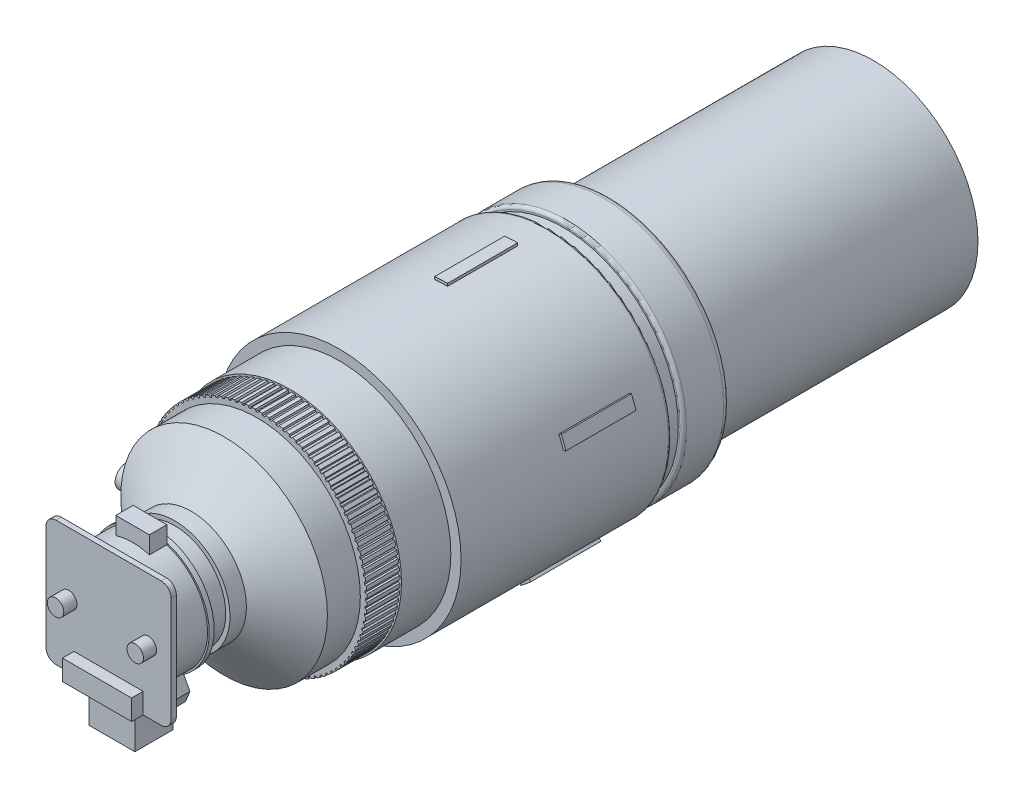
SolidWorks part; units mm, degrees
ref_plane "Front Plane" through (0, 0, 0) normal (0, 0, 1) x (1, 0, 0)
ref_plane "Top Plane" through (0, 0, 0) normal (0, 1, 0) x (1, 0, 0)
ref_plane "Right Plane" through (0, 0, 0) normal (1, 0, 0) x (0, 0, -1)
sketch "Sketch1" plane through (0, 0, 0) normal (0, 0, 1) x (1, 0, 0)
  circle A0 centre (0, 0) radius 31.75
  dimension "D1" = 63.5
extrude "Boss-Extrude1" add sketch "Sketch1" along normal blind 80
sketch "Sketch2" plane through (0, 0, 80) normal (0, 0, 1) x (1, 0, 0)
  circle A0 centre (0, 0) radius 36.5
  dimension "D1" = 73
extrude "Boss-Extrude2" add sketch "Sketch2" along normal blind 14.3
fillet "Fillet1" radius 2 1 edges at (36.5, 0, 80)
sketch "Sketch3" plane through (0, 0, 94.3) normal (0, 0, 1) x (1, 0, 0)
  circle A0 centre (0, 0) radius 35
  dimension "D1" = 70
extrude "Boss-Extrude3" add sketch "Sketch3" along normal blind 4
sketch "Sketch4" plane through (0, 0, 98.3) normal (0, 0, 1) x (1, 0, 0)
  circle A0 centre (0, 0) radius 37
  dimension "D1" = 74
extrude "Boss-Extrude4" add sketch "Sketch4" along normal blind 64
fillet "Fillet2" radius 1 2 edges at (37, 0, 98.3) (36.5, 0, 94.3)
sketch "Sketch5" plane through (0, 0, 162.3) normal (0, 0, 1) x (1, 0, 0)
  circle A0 centre (0, 0) radius 33.9
  dimension "D1" = 67.8
extrude "Boss-Extrude5" add sketch "Sketch5" along normal blind 15
sketch "Sketch6" plane through (0, 0, 177.3) normal (0, 0, 1) x (1, 0, 0)
  circle A0 centre (0, 0) radius 33.4
  dimension "D1" = 66.8
extrude "Boss-Extrude6" add sketch "Sketch6" along normal blind 10
sketch "Sketch7" plane through (0, 0, 187.3) normal (0, 0, 1) x (1, 0, 0)
  line L0 (0, 0) -> (0, 33.4) construction
  line L1 (-0.5, 33.3963) -> (-0.3, 32.9)
  line L2 (-0.3, 32.9) -> (0, 32.9)
  line L3 (0, 32.9) -> (0.3, 32.9)
  line L4 (0.3, 32.9) -> (0.5, 33.3963)
  circle A0 centre (0, 0) radius 33.4 construction
  circle A1 centre (0, 0) radius 33.4
  circle M6 centre (0, 0) radius 33.4
  dimension "D1" = 0.5
  dimension "D2" = 0.6
  dimension "D3" = 1
extrude "Cut-Extrude1" cut sketch "Sketch7" against normal up to surface (10 mm away) contours L2 L0 A1 L1 | L0 L3 L4 M6 region at (-0.2041, 33.1702, 187.3) region at (0.2041, 33.1702, 187.3) up to face at (33.4, 0, 177.3)
pattern_circular "CirPattern1" count 100 over 360 about axis through (0, 0, 177.3) along (0, 0, 1) of "Cut-Extrude1"
sketch "Sketch8" plane through (0, 0, 187.3) normal (0, 0, 1) x (1, 0, 0)
  circle A0 centre (0, 0) radius 31.4
  dimension "D1" = 62.8
extrude "Boss-Extrude7" add sketch "Sketch8" along normal blind 10
sketch "Sketch9" plane through (0, 0, 0) normal (1, 0, 0) x (0, 0, -1)
  line L0 (-197.3, 31.4) -> (-197.3, -31.4) construction
  line L1 (-197.3, 31.4) -> (-197.3, 0)
  line L2 (-197.3, 0) -> (-207.3, 0) construction
  line L3 (-207.3, 0) -> (-207.3, 16.8) construction
  line L4 (-207.3, 16.8) -> (-197.3, 31.4)
  line L5 (-207.3, 16.8) -> (-212.3, 16.8)
  line L6 (-212.3, 16.8) -> (-212.3, 0)
  line L7 (-212.3, 0) -> (-197.3, 0)
  dimension "D1" = 16.8
  dimension "D2" = 5
  dimension "D3" = 10
revolve "Revolve1" add sketch "Sketch9" angle 360 about L7
sketch "Sketch10" plane through (0, 0, 0) normal (1, 0, 0) x (0, 0, -1)
  line L0 (-99.3, 37) -> (-162.3, 37) construction
  line L1 (-108.1, 37) -> (-129.4, 37)
  line L2 (-108.1, 37) -> (-108.1, 37.8)
  line L3 (-108.1, 37.8) -> (-129.4, 37.8)
  line L4 (-129.4, 37.8) -> (-129.4, 37)
  line L5 (-98.3, -35) -> (-98.3, 35) construction
  line L6 (0, 0) -> (-212.3, 0) construction
  line L7 (-212.3, 16.8) -> (-212.3, -16.8) construction
  dimension "D1" = 21.3
  dimension "D2" = 0.8
  dimension "D3" = 9.8
revolve "Revolve2" add sketch "Sketch10" angle 6 about L6
pattern_circular "CirPattern2" count 5 over 360 about axis through (0, 0, 99.3) along (0, 0, 1) of "Revolve2"
sketch "Sketch11" plane through (0, 0, 212.3) normal (0, 0, 1) x (1, 0, 0)
  circle A0 centre (0, 0) radius 15.5
  dimension "D1" = 31
extrude "Boss-Extrude8" add sketch "Sketch11" along normal blind 6
sketch "Sketch12" plane through (0, 0, 218.3) normal (0, 0, 1) x (1, 0, 0)
  circle A0 centre (0, 0) radius 18
  dimension "D1" = 36
extrude "Boss-Extrude9" add sketch "Sketch12" along normal blind 1.5
sketch "Sketch13" plane through (0, 0, 219.8) normal (0, 0, 1) x (1, 0, 0)
  circle A0 centre (0, 0) radius 17.5
  dimension "D1" = 35
extrude "Boss-Extrude10" add sketch "Sketch13" along normal blind 11
sketch "Sketch14" plane through (0, 0, 219.8) normal (0, 0, 1) x (1, 0, 0)
  line L0 (0, 0) -> (0, 24.1757) construction
  line L1 (0, 22.0404) -> (5.1, 22.0404)
  line L2 (5.1, 22.0404) -> (5.1, 16.7404)
  line L3 (0, 22.0404) -> (-5.1, 22.0404)
  line L4 (-5.1, 22.0404) -> (-5.1, 16.7404)
  circle A0 centre (0, 0) radius 17.5 construction
  circle A1 centre (0, 0) radius 17.5
  circle M3 centre (0, 0) radius 17.5
  circle M4 centre (0, 0) radius 18
  dimension "D1" = 10.2
  dimension "D2" = 5.3
extrude "Boss-Extrude11" add sketch "Sketch14" along normal blind 5.3 separate body contours L0 L3 L4 M4 | L0 L2 L1 M4 | L0 A1 L2 M4 | L0 L4 M3 M4 region at (-2.5682, 17.4998, 219.8) region at (2.5682, 17.4998, 219.8) region at (-2.6229, 19.8927, 219.8) region at (2.6229, 19.8927, 219.8)
sketch "Sketch15" plane through (0, 0, 219.8) normal (0, 0, 1) x (1, 0, 0)
  line L0 (0, 0) -> (0, -30.9596) construction
  line L1 (10, -14.3614) -> (12.15, -18.3146)
  line L2 (12.15, -18.3146) -> (10.7889, -21.6473)
  line L3 (10.7889, -21.6473) -> (7, -23.4596)
  line L4 (7, -23.4596) -> (7, -30.9596)
  line L5 (7, -30.9596) -> (-7, -30.9596)
  line L6 (0, 0) -> (10.4352, -21.8165) construction
  line L7 (5.1, 22.0404) -> (-5.1, 22.0404) construction
  line L8 (-10, -14.3614) -> (-12.15, -18.3146)
  line L9 (-12.15, -18.3146) -> (-10.7889, -21.6473)
  line L10 (-10.7889, -21.6473) -> (-7, -23.4596)
  line L11 (-7, -23.4596) -> (-7, -30.9596)
  circle A0 centre (0, 0) radius 17.5 construction
  circle A1 centre (0, 0) radius 17.5
  circle M8 centre (0, 0) radius 17.5
  circle M9 centre (0, 0) radius 18
  dimension "D1" = 14
  dimension "D2" = 53
  dimension "D3" = 7.5
  dimension "D4" = 24.3
  dimension "D5" = 20
  dimension "D6" = 3.6
  dimension "D7" = 4.2
  dimension "D8" = 4.5
extrude "Boss-Extrude12" add sketch "Sketch15" along normal blind 11.6 contours L10 L11 L5 L4 L3 L2 L1 L8 L9 M9 | L8 L1 M8 M9 region at (9.9374, -14.6817, 219.8) region at (0, -22.9881, 219.8)
sketch "Sketch16" plane through (0, 0, 231.4) normal (0, 0, 1) x (1, 0, 0)
  line L0 (-7, -23.4596) -> (-7, -7.635)
  line L1 (7, -23.4596) -> (7, -7.635)
  line L2 (0, 0) -> (52.2269, 0) construction
  line L3 (-7, -20) -> (7, -20)
  line L9 (-10.7889, -21.6473) -> (-7, -23.4596)
  line L10 (-7, -23.4596) -> (-7, -30.9596)
  line L11 (-7, -30.9596) -> (7, -30.9596)
  line L12 (7, -30.9596) -> (7, -23.4596)
  line L13 (7, -23.4596) -> (10.7889, -21.6473)
  line L14 (10.7889, -21.6473) -> (12.15, -18.3146)
  line L15 (12.15, -18.3146) -> (10, -14.3614)
  line L16 (-10, -14.3614) -> (-12.15, -18.3146)
  line L17 (-12.15, -18.3146) -> (-10.7889, -21.6473)
  line L18 (-10.7889, -21.6473) -> (-7, -23.4596)
  line L19 (-7, -23.4596) -> (-7, -30.9596)
  line L20 (-7, -30.9596) -> (7, -30.9596)
  line L21 (7, -30.9596) -> (7, -23.4596)
  line L22 (7, -23.4596) -> (10.7889, -21.6473)
  line L23 (10.7889, -21.6473) -> (12.15, -18.3146)
  line L24 (12.15, -18.3146) -> (10, -14.3614)
  line L25 (-10, -14.3614) -> (-12.15, -18.3146)
  line L26 (-12.15, -18.3146) -> (-10.7889, -21.6473)
  arc A1 (-10, -14.3614) -> (10, -14.3614) centre (0, 0) ccw
  arc A2 (-10, -14.3614) -> (10, -14.3614) centre (0, 0) ccw
  line M13 (-10.7889, -21.6473) -> (-7, -23.4596)
  line M17 (7, -23.4596) -> (10.7889, -21.6473)
  line M18 (10.7889, -21.6473) -> (12.15, -18.3146)
  line M19 (12.15, -18.3146) -> (10, -14.3614)
  arc M20 (10, -14.3614) -> (-10, -14.3614) centre (0, 0) cw
  line M21 (-10, -14.3614) -> (-12.15, -18.3146)
  line M22 (-12.15, -18.3146) -> (-10.7889, -21.6473)
  dimension "D2" = 20
  dimension "D1" = 0
extrude "Cut-Extrude2" cut sketch "Sketch16" against normal blind 6 contours L0 M13 M20 M21 M22 | L0 L3 L1 M20 | L1 M17 M18 M19 M20 region at (-9.1639, -18.8559, 231.4) region at (0, -18.4793, 231.4) region at (9.1639, -18.8559, 231.4)
sketch "Sketch17" plane through (0, 0, 230.8) normal (0, 0, 1) x (1, 0, 0)
  line L1 (-19, -19) -> (19, -19)
  line L2 (-19, -19) -> (-19, 19)
  line L3 (-19, 19) -> (19, 19)
  line L4 (19, -19) -> (19, 19)
  line L5 (-19, -19) -> (19, 19) construction
  line L6 (-19, 19) -> (19, -19) construction
  point P0 (0, 0)
  dimension "D1" = 38
extrude "Boss-Extrude13" add sketch "Sketch17" along normal blind 1.6
fillet "Fillet3" radius 3 4 edges at (19, 19, 231.6) (19, -19, 231.6) (-19, -19, 231.6) (-19, 19, 231.6)
sketch "Sketch18" plane through (0, 0, 232.4) normal (0, 0, 1) x (1, 0, 0)
  line L0 (0, 0) -> (19, 0) construction
  line L1 (19, -16) -> (19, 16) construction
  line L2 (0, 0) -> (-19, 0) construction
  line L3 (-19, 16) -> (-19, -16) construction
  line L4 (-12.1, 0) -> (0, 22.0404) construction
  line L5 (5.1, 22.0404) -> (-5.1, 22.0404) construction
  line L6 (0, 22.0404) -> (12.1, 0) construction
  circle A0 centre (-12.1, 0) radius 2.5
  circle A1 centre (12.1, 0) radius 2.5
  dimension "D1" = 5
  dimension "D2" = 24.2
extrude "Boss-Extrude14" add sketch "Sketch18" along normal blind 4
sketch "Sketch19" plane through (0, 0, 232.4) normal (0, 0, 1) x (1, 0, 0)
  line L0 (-16, -19) -> (16, -19) construction
  line L1 (-10.5, -19) -> (10.5, -19)
  line L2 (-10.5, -19) -> (-10.5, -12.8)
  line L3 (-10.5, -12.8) -> (10.5, -12.8)
  line L4 (10.5, -19) -> (10.5, -12.8)
  line L5 (0, 0) -> (0, -12.8) construction
  dimension "D1" = 6.2
  dimension "D2" = 21
extrude "Boss-Extrude15" add sketch "Sketch19" along normal blind 3.5
sketch "Sketch20" plane through (0, 0, 0) normal (1, 0, 0) x (0, 0, -1)
  line L0 (-207.3, 0) -> (-187.2978, 0) construction
  line L1 (-207.3, -16.8) -> (-207.3, 16.8) construction
  line L2 (-190.9, 31.402) -> (-190.9, 0) construction
  line L4 (-187.3, 31.4) -> (-187.3, -31.4) construction
  circle A0 centre (-190.9, 0) radius 3.5
  dimension "D1" = 7
  dimension "D2" = 3.6
extrude "Boss-Extrude19" add sketch "Sketch20" against normal blind 36
sketch "Sketch21" plane through (0, -30.9596, 0) normal (0, -1, 0) x (1, 0, 0)
  line L0 (-7, 225.6) -> (7, 225.6) construction
  line L1 (-7, 231.4) -> (-7, 219.8) construction
  line L2 (7, 231.4) -> (7, 219.8) construction
  line L3 (0, 231.4) -> (0, 219.8) construction
  line L4 (7, 231.4) -> (-7, 231.4) construction
  line L5 (7, 219.8) -> (-7, 219.8) construction
  circle A0 centre (0, 225.6) radius 2.75
  dimension "D1" = 5.5
extrude "Cut-Extrude3" cut sketch "Sketch21" against normal blind 5
equation "\"8g\"=10"
